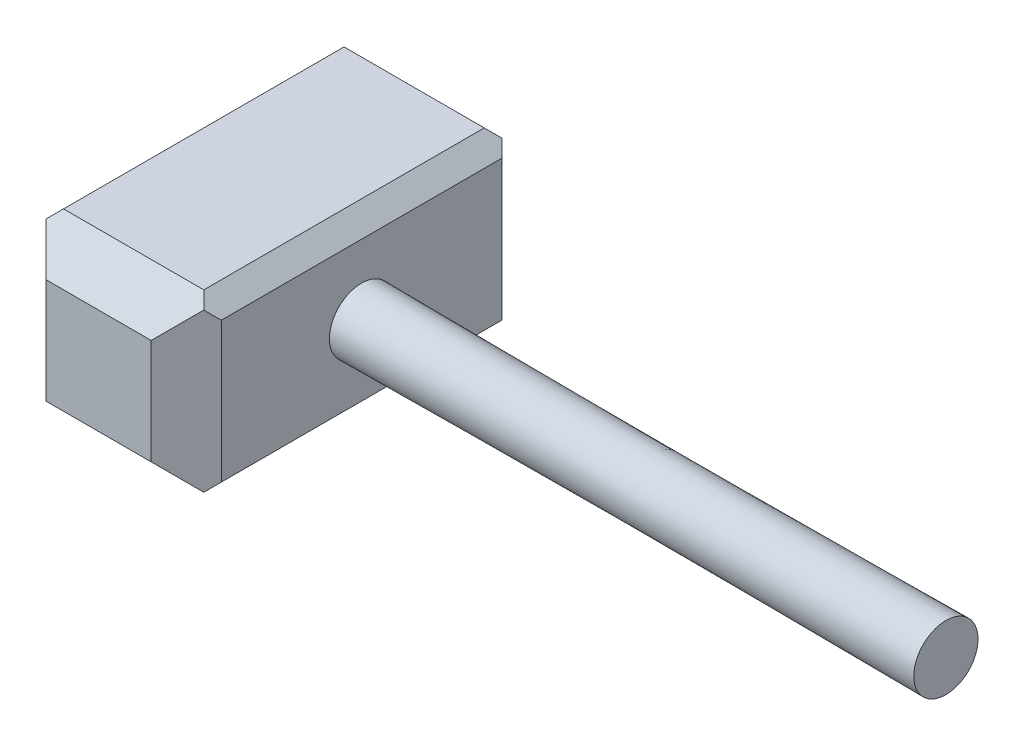
SolidWorks part; units mm, degrees
material "Acero galvanizado"
ref_plane "Alzado" through (0, 0, 0) normal (0, 0, 1) x (1, 0, 0)
ref_plane "Planta" through (0, 0, 0) normal (0, 1, 0) x (1, 0, 0)
ref_plane "Vista lateral" through (0, 0, 0) normal (1, 0, 0) x (0, 0, -1)
sketch "Croquis2" plane through (0, 0, 0) normal (1, 0, 0) x (0, 0, -1)
  line L1 (-150, 75) -> (150, 75)
  line L2 (-150, 75) -> (-150, -75)
  line L3 (-150, -75) -> (150, -75)
  line L4 (150, 75) -> (150, -75)
  line L5 (-150, 75) -> (150, -75) construction
  line L6 (-150, -75) -> (150, 75) construction
  point P0 (0, 0)
  dimension "D1" = 300
  dimension "D2" = 150
ref_plane "Plano1" through (0, 0, 0) normal (1, 0, 0) x (0, 0, -1)
ref_plane "Plano2" through (150, 0, 0) normal (1, 0, 0) x (0, 0, -1)
sketch "Croquis3" plane through (150, 0, 0) normal (1, 0, 0) x (0, 0, -1)
  line L1 (-150, 75) -> (150, 75)
  line L2 (-150, 75) -> (-150, -75)
  line L3 (-150, -75) -> (150, -75)
  line L4 (150, 75) -> (150, -75)
  line L5 (-150, 75) -> (150, -75) construction
  line L6 (-150, -75) -> (150, 75) construction
  point P0 (0, 0)
loft "Recubrir1" add profiles "Croquis3", "Croquis2" connector at (150, -75, 150) connector at (0, -75, 150)
ref_plane "Plano3" through (150, 0, 0) normal (1, 0, 0) x (0, 0, -1)
sketch "Croquis4" plane through (150, 0, 0) normal (1, 0, 0) x (0, 0, -1)
  circle A0 centre (0, 0) radius 27.5
  dimension "D1" = 55
ref_plane "Plano4" through (650, 0, 0) normal (1, 0, 0) x (0, 0, -1)
sketch "Croquis5" plane through (650, 0, 0) normal (1, 0, 0) x (0, 0, -1)
  circle A0 centre (0, 0) radius 27.5
  dimension "D1" = 55
loft "Recubrir2" add profiles "Croquis4", "Croquis5" connector at (150, 5.1869, -27.0064) connector at (650, 19.5794, -19.3106)
ref_plane "Plano5" through (0, 0, 0) normal (1, 0, 0) x (0, 0, -1)
sketch "Croquis6" plane through (0, 0, 0) normal (1, 0, 0) x (0, 0, -1)
  circle A0 centre (0, 0) radius 45
  dimension "D1" = 90
ref_plane "Plano6" through (-10, 0, 0) normal (1, 0, 0) x (0, 0, -1)
sketch "Croquis7" plane through (-10, 0, 0) normal (1, 0, 0) x (0, 0, -1)
  circle A0 centre (0, 0) radius 45
  dimension "D1" = 90
loft "Recubrir4" add profiles "Croquis6", "Croquis7" connector at (0, 44.9804, 1.3287) connector at (-10, 44.4851, -6.7881)
chamfer "Chaflán2" distance 30 angle 45 4 edges
chamfer "Chaflán3" distance 30 angle 45 1 edges
chamfer "Chaflán4" distance 30 angle 45 3 edges
chamfer "Chaflán5" distance 15 angle 45 4 edges
